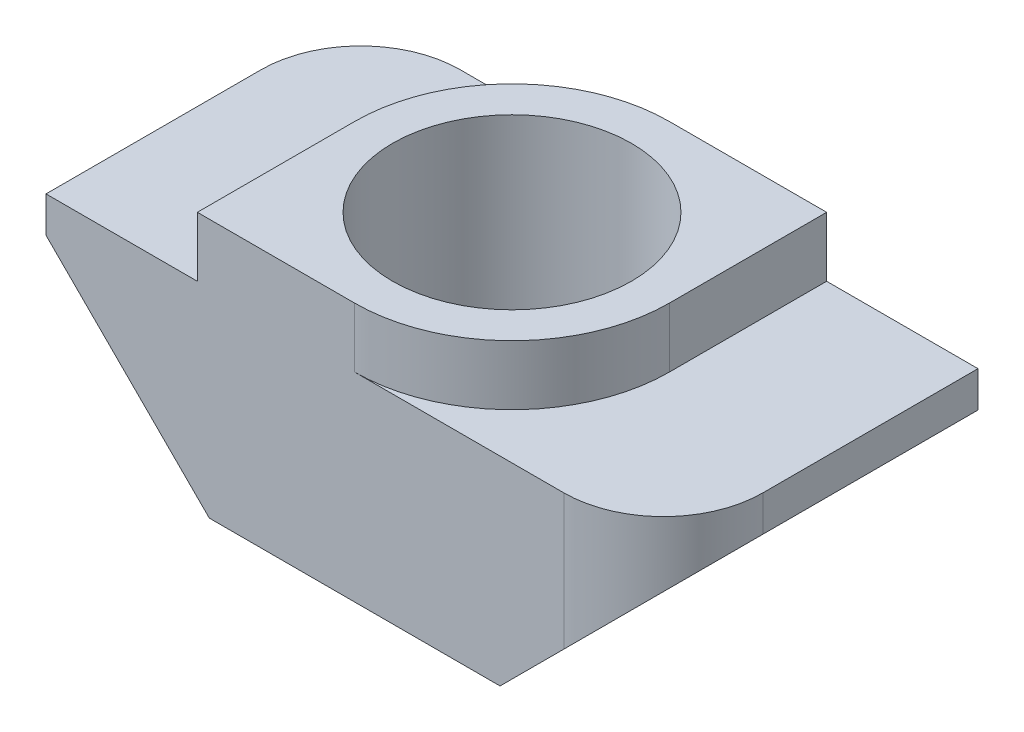
SolidWorks part; units mm, degrees
ref_plane "前视基准面" through (0, 0, 0) normal (0, 0, 1) x (1, 0, 0)
ref_plane "上视基准面" through (0, 0, 0) normal (0, 1, 0) x (1, 0, 0)
ref_plane "右视基准面" through (0, 0, 0) normal (1, 0, 0) x (0, 0, -1)
other "Configuration Table"
sketch "草图1" plane through (0, 0, 0) normal (0, 1, 0) x (1, 0, 0)
  line L1 (0, 0) -> (15.5, 0)
  line L2 (0, 0) -> (0, 7.9)
  line L3 (0, 7.9) -> (15.5, 7.9)
  line L4 (15.5, 0) -> (15.5, 7.9)
  dimension "D1" = 7.9
  dimension "D2" = 15.5
extrude "凸台-拉伸1" add sketch "草图1" along normal blind 5
sketch "草图2" plane through (0, 0, 0) normal (0, 1, 0) x (1, 0, 0)
  line L0 (15.5, 7.9) -> (0, 7.9) construction
  line L1 (3.8, 3.95) -> (3.8, 0)
  line L2 (0, 0) -> (15.5, 0) construction
  line L3 (3.8, 0) -> (7.75, 0)
  line L4 (7.75, 7.9) -> (11.7, 7.9)
  line L5 (11.7, 7.9) -> (11.7, 3.95)
  circle A0 centre (7.75, 3.95) radius 3
  arc A1 (7.75, 0) -> (11.7, 3.95) centre (7.75, 3.95) ccw
  arc A2 (7.75, 7.9) -> (3.8, 3.95) centre (7.75, 3.95) ccw
  dimension "D3" = 6
  dimension "D1" = 7.75
  dimension "D2" = 3.95
extrude "凸台-拉伸2" add sketch "草图2" along normal blind 1.5 from surface contours A1 L5 L4 A2 L1 L3 starting at face at (7.75, 5, -3.95)
sketch "草图3" plane through (0, 0, 0) normal (0, 0, 1) x (1, 0, 0)
  line L0 (0, 4.1) -> (4.1, 0)
  line L1 (0, 5) -> (0, 0) construction
  line L2 (0, 0) -> (15.5, 0) construction
  line L3 (4.1, 0) -> (11.4, 0) construction
  line L4 (11.4, 0) -> (15.5, 4.1)
  line L5 (15.5, 5) -> (15.5, 0) construction
  line L6 (15.5, 4.1) -> (0, 4.1) construction
  line L8 (7.75, 9.0744) -> (7.75, -3.0876) construction
  line L9 (0, 4.1) -> (0, 0)
  line L10 (0, 0) -> (4.1, 0)
  line L11 (15.5, 4.1) -> (15.5, 0)
  line L12 (15.5, 0) -> (11.4, 0)
  dimension "D1" = 7.3
  dimension "D2" = 135
  dimension "D3" = 7.75
extrude "切除-拉伸2" cut sketch "草图3" against normal through all
sketch "草图4" plane through (0, 0, 0) normal (0, 1, 0) x (1, 0, 0)
  line L0 (0, 7.9) -> (0, 0) construction
  line L1 (7.75, 7.9) -> (0, 7.9) construction
  line L2 (2.5, 7.9) -> (0, 7.9)
  line L3 (0, 7.9) -> (0, 5.4)
  line L4 (-2.7249, 3.95) -> (18.4087, 3.95) construction
  line L5 (7.75, 9.8145) -> (7.75, -2.2928) construction
  line L8 (13, 0) -> (15.5, 0)
  line L9 (15.5, 0) -> (15.5, 2.5)
  line L10 (15.5, 0) -> (15.5, 7.9) construction
  line L11 (7.75, 0) -> (15.5, 0) construction
  arc A0 (0, 5.4) -> (2.5, 7.9) centre (2.5, 5.4) cw
  arc A2 (15.5, 2.5) -> (13, 0) centre (13, 2.5) cw
  dimension "D1" = 2.5
  dimension "D4" = 2.5
  dimension "D2" = 3.95
  dimension "D3" = 7.75
  dimension "D5" = 13
  dimension "D6" = 2.5
extrude "切除-拉伸3" cut sketch "草图4" along normal up to next
extrude "切除-拉伸4" cut sketch "草图2<5>" along normal through all contours A0
sketch "草图2<5>" plane through (0, 0, 0) normal (0, 1, 0) x (1, 0, 0) same geometry as "草图2"
